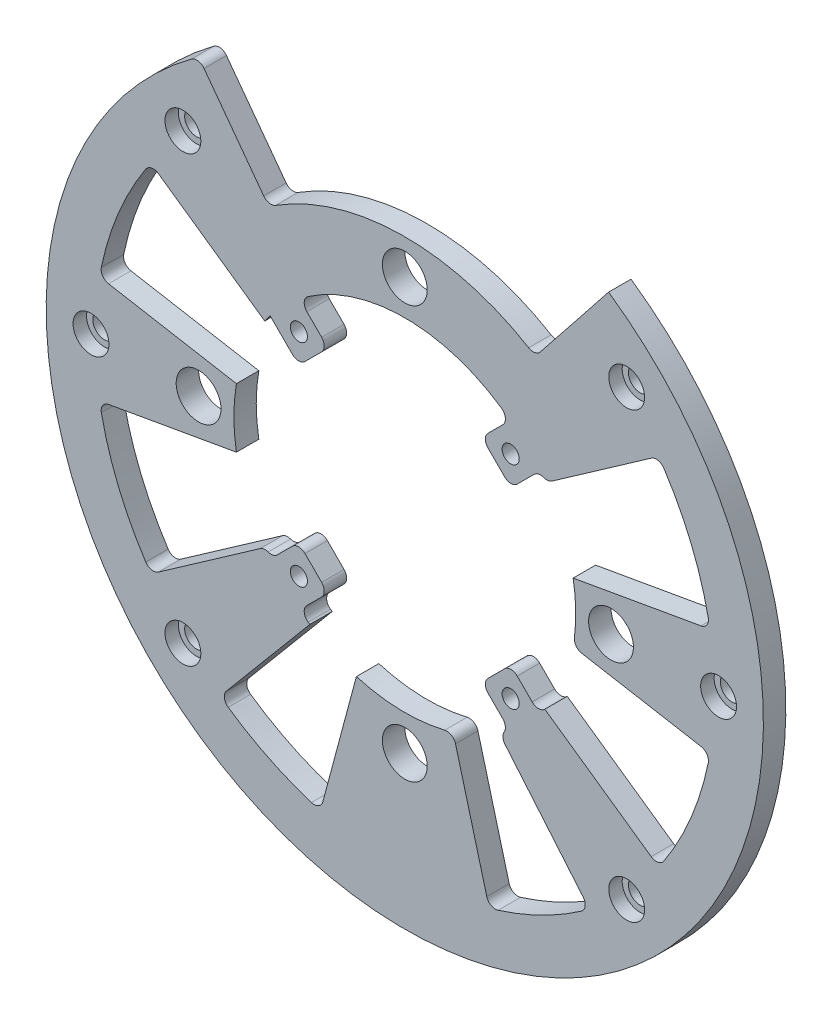
SolidWorks part; units mm, degrees
ref_plane "Front Plane" through (0, 0, 0) normal (0, 0, 1) x (1, 0, 0)
ref_plane "Top Plane" through (0, 0, 0) normal (0, 1, 0) x (1, 0, 0)
ref_plane "Right Plane" through (0, 0, 0) normal (1, 0, 0) x (0, 0, -1)
sketch "Sketch1" plane through (0, 0, 0) normal (0, 0, 1) x (1, 0, 0)
  circle A0 centre (0, 0) radius 48.4359
  circle A1 centre (0, 0) radius 101.6
extrude "Extrude1" add sketch "Sketch1" along normal blind 6.35
sketch "Sketch4" plane through (0, 0, 6.35) normal (0, 0, 1) x (1, 0, 0)
  point P0 (62.8618, -62.8618)
  point P1 (88.9, 0)
  point P2 (62.8618, 62.8618)
  point P3 (-62.8618, 62.8618)
  point P4 (-88.9, 0)
  point P5 (-62.8618, -62.8618)
hole_wizard "CBORE for 1/4 Socket Head Cap Screw1" positions "Sketch9" profile "Sketch8" counterbore size "1/4" standard "Ansi Inch" end condition through all
sketch "Sketch9" plane through (0, 0, 6.35) normal (0, 0, 1) x (1, 0, 0)
  point P1 (62.8618, -62.8618)
  point P3 (88.9, 0)
  point P5 (62.8618, 62.8618)
  point P7 (-62.8618, 62.8618)
  point P9 (-88.9, 0)
  point P11 (-62.8618, -62.8618)
sketch "Sketch8" plane through (62.8618, -62.8618, 6.35) normal (1, 0, 0) x (0, -1, 0)
  line L0 (0, 0) -> (0, 6.35)
  line L1 (0, 6.35) -> (3.3147, 6.35)
  line L3 (3.3147, 6.35) -> (3.3147, 3.81)
  line L4 (3.3147, 3.81) -> (5.08, 3.81)
  line L5 (5.08, 3.81) -> (5.08, 0)
  line L7 (5.08, 0) -> (0, 0)
  line L11 (0, -6.35) -> (0, 107.95) construction
  dimension "Thru Hole Dia." = 6.6294
  dimension "Thru Hole Depth" = 6.35
  dimension "C'Bore Dia." = 10.16
  dimension "C'Bore Depth" = 3.81
sketch "Sketch11" plane through (0, 0, 6.35) normal (0, 0, 1) x (1, 0, 0)
  circle A0 centre (0, -95.25) radius 17.78
sketch "Sketch12" plane through (0, 0, 6.35) normal (0, 0, 1) x (1, 0, 0)
  line L0 (-58.42, 0) -> (58.42, 0) construction
  circle A0 centre (0, -58.42) radius 6.35
  circle A1 centre (-58.42, 0) radius 6.35
  circle A2 centre (58.42, 0) radius 6.35
  circle A3 centre (0, 58.42) radius 6.35
  dimension "D1" = 12.7
extrude "Cut-Extrude2" cut sketch "Sketch12" against normal through all
sketch "Sketch13" plane through (0, 0, 6.35) normal (0, 0, 1) x (1, 0, 0)
  line L0 (0, 0) -> (0, -67.9248) construction
  line L1 (0, 0) -> (61.5438, 0) construction
  line L2 (0, 0) -> (29.9999, -29.9999) construction
  line L3 (30.0672, -21.7618) -> (44.904, -36.5986)
  line L4 (44.904, -36.5986) -> (36.5986, -44.904)
  line L5 (30.0672, -21.7618) -> (21.7618, -30.0672)
  line L6 (21.7618, -30.0672) -> (36.5986, -44.904)
  line L7 (-30.0672, -21.7618) -> (-44.904, -36.5986)
  line L8 (-30.0672, -21.7618) -> (-21.7618, -30.0672)
  line L9 (-21.7618, -30.0672) -> (-36.5986, -44.904)
  line L10 (-44.904, -36.5986) -> (-36.5986, -44.904)
  line L11 (-30.0672, 21.7618) -> (-21.7618, 30.0672)
  line L12 (-30.0672, 21.7618) -> (-44.904, 36.5986)
  line L13 (-44.904, 36.5986) -> (-36.5986, 44.904)
  line L14 (-21.7618, 30.0672) -> (-36.5986, 44.904)
  line L15 (30.0672, 21.7618) -> (21.7618, 30.0672)
  line L16 (30.0672, 21.7618) -> (44.904, 36.5986)
  line L17 (21.7618, 30.0672) -> (36.5986, 44.904)
  line L18 (44.904, 36.5986) -> (36.5986, 44.904)
  circle A0 centre (-29.9999, 29.9999) radius 2.4265
  circle A1 centre (29.9999, 29.9999) radius 2.4265
  circle A2 centre (-29.9999, -29.9999) radius 2.4265
  circle A3 centre (29.9999, -29.9999) radius 2.4265
  point P11 (25.9145, -25.9145)
  point P12 (40.7513, -40.7513)
extrude "Extrude2" add sketch "Sketch13" against normal up to surface (6.35 mm away) up to face at (-6.35, 58.42, 0)
sketch "Sketch14" plane through (0, 0, 6.35) normal (0, 0, 1) x (1, 0, 0)
  line L0 (0, -7.6401) -> (0, -64.3895) construction
  line L1 (0, 0) -> (76.0963, 0) construction
  line L2 (36.9784, 57.4547) -> (71.6833, 101.141)
  line L3 (71.6833, 101.141) -> (0, 148.4755)
  line L4 (-71.6833, 101.141) -> (0, 148.4755)
  line L5 (-38.5448, 56.4158) -> (-71.6833, 101.141)
  line L6 (8.6526, -27.5809) -> (23.9004, -84.4864)
  line L7 (14.2276, -25.1624) -> (52.2951, -70.5294)
  line L8 (-71.9231, 50.3611) -> (-23.6786, 16.5799)
  line L9 (-86.468, 15.2466) -> (-28.4671, 5.0195)
  line L10 (-8.6522, -27.581) -> (-23.9004, -84.4864)
  line L11 (-14.2295, -25.1613) -> (-52.2951, -70.5294)
  line L12 (-86.468, -15.2466) -> (-28.4671, -5.0195)
  line L13 (-71.9231, -50.3611) -> (-23.6786, -16.5799)
  line L14 (23.6786, -16.5799) -> (71.9231, -50.3611)
  line L15 (28.4671, -5.0195) -> (86.468, -15.2466)
  line L16 (28.4671, 5.0195) -> (86.468, 15.2466)
  line L17 (23.6786, 16.5799) -> (71.9231, 50.3611)
  arc A0 (23.9004, -84.4864) -> (52.2951, -70.5294) centre (0, 0) ccw
  arc A1 (-52.2951, -70.5294) -> (-23.9004, -84.4864) centre (0, 0) ccw
  arc A2 (-86.468, -15.2466) -> (-71.9231, -50.3611) centre (0, 0) ccw
  arc A3 (-71.9231, 50.3611) -> (-86.468, 15.2466) centre (0, 0) ccw
  arc A4 (86.468, 15.2466) -> (71.9231, 50.3611) centre (0, 0) ccw
  arc A5 (71.9231, -50.3611) -> (86.468, -15.2466) centre (0, 0) ccw
  arc A6 (36.9784, 57.4547) -> (-38.5448, 56.4158) centre (0, 0) ccw
  arc A7 (28.4671, 5.0195) -> (23.6786, 16.5799) centre (0, 0) ccw
  arc A8 (23.6786, -16.5799) -> (28.4671, -5.0195) centre (0, 0) ccw
  arc A9 (8.6526, -27.5809) -> (14.2276, -25.1624) centre (0, 0) ccw
  arc A10 (-14.2295, -25.1613) -> (-8.6522, -27.581) centre (0, 0) ccw
  arc A11 (-28.4671, -5.0195) -> (-23.6786, -16.5799) centre (0, 0) ccw
  arc A12 (-23.6786, 16.5799) -> (-28.4671, 5.0195) centre (0, 0) ccw
  dimension "D5" = 75
  dimension "D1" = 10
  dimension "D2" = 15
  dimension "D3" = 25
  dimension "D4" = 25
extrude "Cut-Extrude3" cut sketch "Sketch14" against normal blind 6.35
fillet "Fillet1" radius 2.54 23 edges at (47.7, -8.4108, 3.175) (29.8439, -38.1494, 3.175) (-58.3635, 83.164, 3.175) (-30.0672, -21.7618, 3.175) (-30.0672, 21.7618, 3.175) (30.0672, 21.7618, 3.175) (-21.7618, -30.0672, 3.175) (-21.7618, 30.0672, 3.175) (21.7618, -30.0672, 3.175) (30.0672, -21.7618, 3.175) (21.7618, 30.0672, 3.175) (86.468, 15.2466, 3.175) (71.9231, 50.3611, 3.175) (-86.468, -15.2466, 3.175) (23.9004, -84.4864, 3.175) (52.2951, -70.5294, 3.175) (-71.9231, 50.3611, 3.175) (86.468, -15.2466, 3.175) (-71.9231, -50.3611, 3.175) (71.9231, -50.3611, 3.175) (-23.9004, -84.4864, 3.175) (-52.2951, -70.5294, 3.175) (-86.468, 15.2466, 3.175)
fillet "Fillet2" radius 2.54 2 edges at (-38.1494, -29.8439, 3.175) (39.6763, 27.7817, 3.175)
fillet "Fillet3" radius 2.54 4 edges at (38.1494, -29.8439, 3.175) (26.9079, -40.2741, 3.175) (13.71, -46.455, 3.175) (-29.8439, 38.1494, 3.175)
fillet "Fillet6" radius 2.54 4 edges at (-29.8439, -38.1494, 3.175) (-39.6763, -27.7817, 3.175) (38.1494, 29.8439, 3.175) (29.8439, 38.1494, 3.175)
fillet "Fillet9" radius 2.54 2 edges at (-38.5448, 56.4158, 3.175) (36.9784, 57.4547, 3.175)
